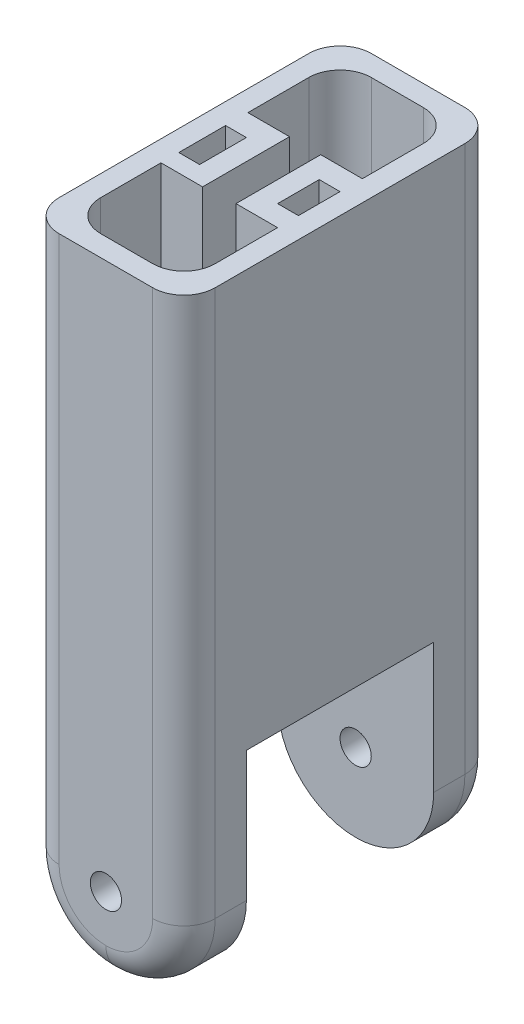
SolidWorks part; units mm, degrees
ref_plane "Front Plane" through (0, 0, 0) normal (0, 0, 1) x (1, 0, 0)
ref_plane "Top Plane" through (0, 0, 0) normal (0, 1, 0) x (1, 0, 0)
ref_plane "Right Plane" through (0, 0, 0) normal (1, 0, 0) x (0, 0, -1)
sketch "Sketch1" plane through (0, 0, 0) normal (0, 1, 0) x (1, 0, 0)
  line L0 (0, 0) -> (-10.7454, 0) construction
  line L1 (-7.5, -15) -> (7.5, -15)
  line L2 (-7.5, -15) -> (-7.5, 15)
  line L3 (-7.5, 15) -> (7.5, 15)
  line L4 (7.5, -15) -> (7.5, 15)
  line L5 (-7.5, -15) -> (7.5, 15) construction
  line L6 (-7.5, 15) -> (7.5, -15) construction
  line L7 (-5.5, -13) -> (5.5, -13)
  line L8 (-5.5, -13) -> (-5.5, -4.2085)
  line L9 (-5.5, 13) -> (5.5, 13)
  line L10 (5.5, -13) -> (5.5, -4)
  line L11 (-5.5, -13) -> (5.5, 13) construction
  line L12 (-5.5, 13) -> (5.5, -13) construction
  line L13 (-10.7454, 0) -> (11.7241, 0) construction
  line L14 (-5.5, 4.1445) -> (-1.5, 4.1445)
  line L15 (-1.5, 4.1445) -> (-1.5, -4.2085)
  line L16 (-1.5, -4.2085) -> (-5.5, -4.2085)
  line L17 (-5.5, 2) -> (-3.5, 2)
  line L18 (-3.5, 2) -> (-3.5, -2.4963)
  line L19 (-3.5, -2.4963) -> (-5.5, -2.4963)
  line L20 (5.5, 4.1445) -> (1.5, 4.1445)
  line L21 (1.5, 4.1445) -> (1.5, -4)
  line L22 (1.5, -4) -> (5.5, -4)
  line L23 (5.5, 2) -> (3.5, 2)
  line L24 (3.5, 2) -> (3.5, -2)
  line L25 (3.5, -2) -> (5.5, -2)
  line L26 (-5.5, 4.1445) -> (-5.5, 13)
  line L27 (5.5, 4.1445) -> (5.5, 13)
  line L28 (-5.5, 2) -> (-5.5, -2.4963)
  line L29 (5.5, 2) -> (5.5, -2)
  point P0 (0, 0)
  point P6 (0, 0)
  dimension "D1" = 2
  dimension "D2" = 2
  dimension "D3" = 2
  dimension "D4" = 2
  dimension "D5" = 2
  dimension "D6" = 2
  dimension "D7" = 2
  dimension "D8" = 2
  dimension "D9" = 2
  dimension "D10" = 2
  dimension "D11" = 30
  dimension "D12" = 15
extrude "Boss-Extrude1" add sketch "Sketch1" along normal blind 40
sketch "Sketch2" plane through (0, 0, 0) normal (0, -1, 0) x (1, 0, 0)
  line L0 (-7.5, -15) -> (-7.5, 15) construction
  line L1 (7.5, 15) -> (-7.5, 15)
  line L2 (7.5, 15) -> (7.5, 9)
  line L3 (7.5, 9) -> (-7.5, 9)
  line L4 (-7.5, 15) -> (-7.5, 9)
  line L6 (7.5, -15) -> (-7.5, -15)
  line L7 (7.5, -15) -> (7.5, -9)
  line L8 (7.5, -9) -> (-7.5, -9)
  line L9 (-7.5, -15) -> (-7.5, -9)
  dimension "D1" = 6
  dimension "D2" = 6
extrude "Boss-Extrude2" add sketch "Sketch2" along normal blind 20
fillet "Fillet1" radius 7.5 4 edges at (-7.5, -20, 12) (-7.5, -20, -12) (7.5, -20, -12) (7.5, -20, 12)
sketch "Sketch3" plane through (0, 0, 15) normal (0, 0, 1) x (1, 0, 0)
  circle A0 centre (0, -12.5) radius 1.5
  dimension "D1" = 3
extrude "Cut-Extrude1" cut sketch "Sketch3" against normal through all
fillet "Fillet2" radius 3 12 edges at (5.3033, -17.8033, 15) (-5.3033, -17.8033, 15) (-5.3033, -17.8033, -15) (7.5, 13.75, 15) (5.5, 20, -13) (-7.5, 13.75, 15) (-7.5, 13.75, -15) (5.3033, -17.8033, -15) (5.5, 20, 13) (-5.5, 20, 13) (7.5, 13.75, -15) (-5.5, 20, -13)
